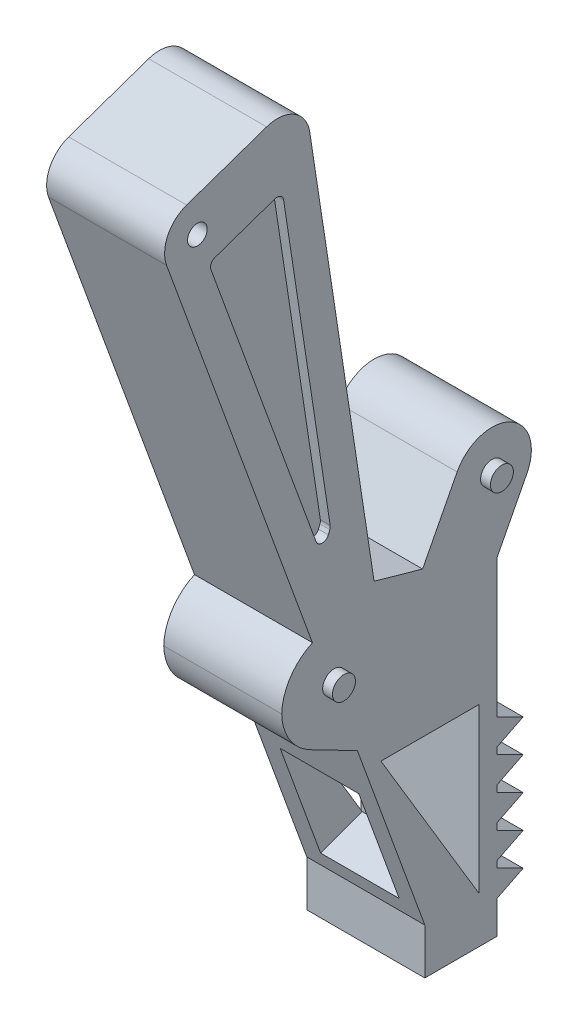
SolidWorks part; units mm, degrees
ref_plane "Front Plane" through (0, 0, 0) normal (0, 0, 1) x (1, 0, 0)
ref_plane "Top Plane" through (0, 0, 0) normal (0, 1, 0) x (1, 0, 0)
ref_plane "Right Plane" through (0, 0, 0) normal (1, 0, 0) x (0, 0, -1)
sketch "Sketch1" plane through (0, 0, 0) normal (1, 0, 0) x (0, 0, -1)
  line L0 (62.8479, 0) -> (38.8518, 65.7586)
  line L1 (38.8518, 65.7586) -> (61.5294, 73.6152)
  line L2 (61.5294, 73.6152) -> (72.242, 3.428)
  line L3 (72.242, 3.428) -> (62.8479, 0)
  line L4 (62.8479, 0) -> (58.1509, -1.714)
  line L5 (58.1509, -1.714) -> (58.1509, -11.714)
  line L6 (58.1509, -11.714) -> (69.7008, -17.6804)
  line L7 (69.7008, -17.6804) -> (79.9849, -45.8627)
  line L8 (79.9849, -45.8627) -> (79.9849, -52.8627)
  line L9 (79.9849, -52.8627) -> (90.9849, -52.8627)
  line L10 (90.9849, -52.8627) -> (90.9849, -2.8627)
  line L11 (90.9849, -2.8627) -> (95.5744, 6.0219)
  line L12 (72.242, 3.428) -> (79.6478, 1.3371)
  line L14 (84.9129, 11.5294) -> (79.6478, 1.3371)
  arc A0 (95.5744, 6.0219) -> (84.9129, 11.5294) centre (90.2437, 8.7757) ccw
  dimension "D1" = 70
  dimension "D2" = 24
  dimension "D3" = 71
  dimension "D4" = 10
  dimension "D5" = 15
  dimension "D6" = 10
  dimension "D7" = 13
  dimension "D8" = 30
  dimension "D9" = 7
  dimension "D10" = 11
  dimension "D11" = 50
  dimension "D12" = 10
  dimension "D13" = 12
extrude "Boss-Extrude1" add sketch "Sketch1" along normal mid plane 18 contours L11 A0 L14 L12 L3 L4 L5 L6 L7 L8 L9 L10 | L3 L2 L1 L0 region at (0, 40.3708, -57.6705) region at (0, -16.3206, -80.3551)
sketch "Sketch2" plane through (9, 0, 0) normal (1, 0, 0) x (0, 0, -1)
  line L0 (88.2849, -45.8627) -> (88.2849, -20.8627)
  line L1 (88.2849, -20.8627) -> (73.2849, -20.8627)
  line L2 (73.2849, -20.8627) -> (88.2849, -45.8627)
  line L3 (79.9849, -45.8627) -> (86.2953, -45.8627) construction
  line L4 (90.9849, -52.8627) -> (90.9849, -2.8627) construction
  dimension "D1" = 25
  dimension "D2" = 15
  dimension "D3" = 0
  dimension "D4" = 2.7
extrude "Cut-Extrude1" cut sketch "Sketch2" against normal blind 25 contours L2 L0 L1
sketch "Sketch3" plane through (9, 0, 0) normal (1, 0, 0) x (0, 0, -1)
  line L0 (90.9849, -45.8627) -> (94.9849, -45.8627)
  line L1 (90.9849, -52.8627) -> (90.9849, -2.8627) construction
  line L2 (94.9849, -45.8627) -> (90.9849, -47.8627)
  line L3 (94.9849, -45.8627) -> (90.9849, -43.8627)
  line L4 (90.9849, -43.8627) -> (90.9849, -47.8627)
  line M19 (90.9849, -52.8627) -> (90.9849, -2.8627)
  dimension "D1" = 4
  dimension "D2" = 2
  dimension "D3" = 4
  dimension "D4" = 5
extrude "Boss-Extrude2" add sketch "Sketch3" against normal blind 18 contours L2 L0 M19 | L0 L3 M19 region at (9, -45.196, -92.3182) region at (9, -46.5293, -92.3182)
pattern_linear "LPattern1" count 5 spacing 5 along (0, 1, 0) of "Boss-Extrude2"
fillet "Fillet2" radius 5 2 edges at (0, 73.6152, -61.5294) (0, 65.7586, -38.8518)
fillet "Fillet3" radius 8 2 edges at (0, -11.714, -58.1509) (0, -1.714, -58.1509)
sketch "Sketch4" plane through (9, 0, 0) normal (1, 0, 0) x (0, 0, -1)
  circle A0 centre (45.2912, 62.6979) radius 1.5
  dimension "D1" = 3
extrude "Cut-Extrude2" cut sketch "Sketch4" against normal blind 18
sketch "Sketch6" plane through (0, 20.3681, -55.8165) normal (0, -0.3428, 0.9394) x (1, 0, 0)
  line L0 (0, -40.5027) -> (0, -70.5027)
  line L1 (9, -40.5027) -> (-9, -40.5027) construction
  line L2 (9, -70.5027) -> (-9, -70.5027) construction
  line L3 (-9, -49.8627) -> (9, -49.8627) construction
  line L4 (9, -40.5027) -> (9, -70.5027) construction
  line L5 (-6, -49.8627) -> (6, -49.8627)
  line L6 (6, -49.8627) -> (6, -67.8923)
  line L7 (6, -67.8923) -> (-6, -67.8923)
  line L8 (-6, -67.8923) -> (-6, -49.8627)
  dimension "D1" = 12
  dimension "D2" = 6
  dimension "D3" = 3
  dimension "D4" = 3
extrude "Cut-Extrude3" cut sketch "Sketch6" against normal blind 8 contours L8 L7 L0 L5 | L7 L6 L5 L0 region at (3, -34.9419, -75.9998) region at (-3, -34.9419, -75.9998)
sketch "Sketch7" plane through (9, 0, 0) normal (1, 0, 0) x (0, 0, -1)
  circle A0 centre (90.2437, 8.7757) radius 1.75
  circle A1 centre (66.1509, -6.8422) radius 1.75
  dimension "D1" = 3.5
  dimension "D2" = 3.5
extrude "Boss-Extrude3" add sketch "Sketch7" along normal blind 1.5
sketch "Sketch9" plane through (9, 0, 0) normal (1, 0, 0) x (0, 0, -1)
  line L0 (58.4409, 60.7121) -> (65.5498, 14.1357)
  line L1 (47.3539, 57.0453) -> (63.3965, 13.0824)
  line L2 (47.9659, 58.333) -> (57.125, 61.5061)
  line L3 (43.6544, 67.4224) -> (55.8558, 71.6496) construction
  line L4 (62.8479, 0) -> (40.5941, 60.9839) construction
  line L5 (62.4353, 67.6795) -> (72.242, 3.428) construction
  line L6 (65.4888, 13.6112) -> (65.2635, 13.0516)
  arc A0 (58.4409, 60.7121) -> (57.125, 61.5061) centre (57.4523, 60.5612) ccw
  arc A1 (47.3539, 57.0453) -> (47.9659, 58.333) centre (48.2933, 57.3881) cw
  arc A2 (65.5498, 14.1357) -> (65.4888, 13.6112) centre (64.5612, 13.9848) cw
  arc A3 (63.3965, 13.0824) -> (65.2635, 13.0516) centre (64.3359, 13.4252) ccw
  dimension "D1" = 1
  dimension "D2" = 1
  dimension "D3" = 5
  dimension "D4" = 5
  dimension "D5" = 10
extrude "Cut-Extrude8" cut sketch "Sketch9" against normal blind 1.5
ref_plane "Plane1" through (0, 0, 0) normal (1, 0, 0) x (0, 0, -1)
mirror "Mirror1" about plane through (0, 0, 0) normal (1, 0, 0) of "Cut-Extrude8", "Boss-Extrude3"
